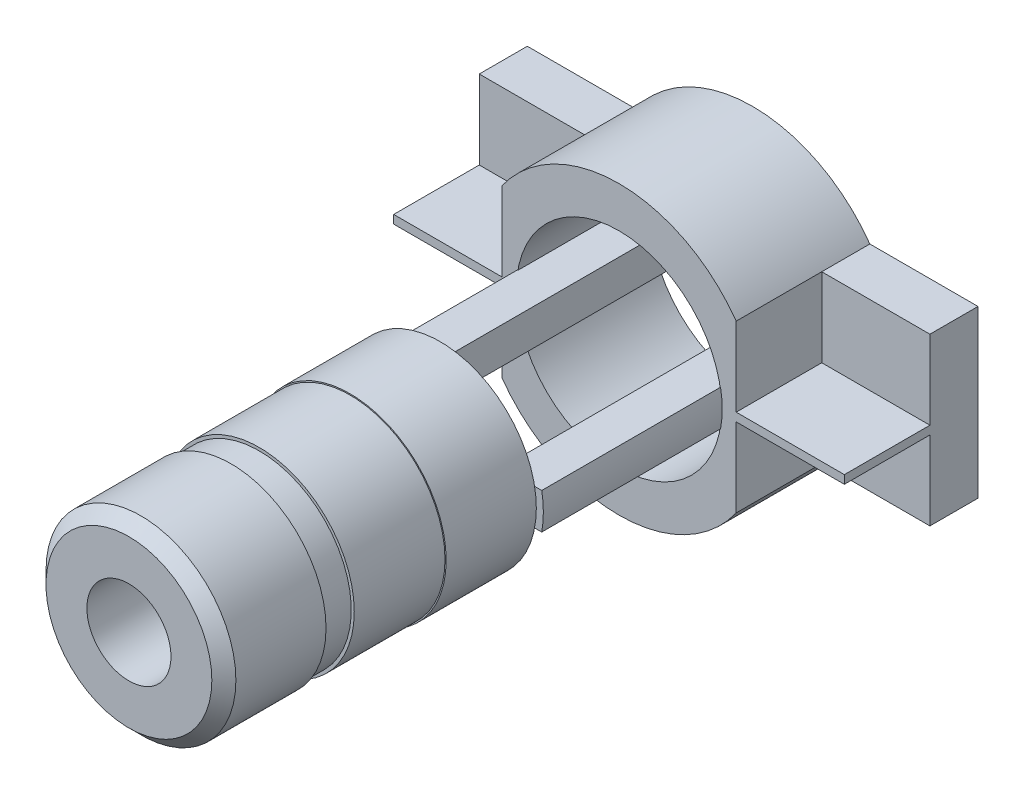
SolidWorks part; units mm, degrees
material "ASTM A36 Steel"
ref_plane "Front Plane" through (0, 0, 0) normal (0, 0, 1) x (1, 0, 0)
ref_plane "Top Plane" through (0, 0, 0) normal (0, 1, 0) x (1, 0, 0)
ref_plane "Right Plane" through (0, 0, 0) normal (1, 0, 0) x (0, 0, -1)
sketch "Sketch1" plane through (0, 0, 0) normal (0, 0, 1) x (1, 0, 0)
  circle A0 centre (0, 0) radius 7.9
  circle A1 centre (0, 0) radius 3.5
  dimension "D1" = 15.8
  dimension "D2" = 7
extrude "Boss-Extrude1" add sketch "Sketch1" along normal blind 18.4
chamfer "Chamfer1" distance 1 angle 45 1 edges at (7.9, 0, 18.4)
ref_plane "Plane7" [suppressed] through (0, 0, 7.5) normal (0, 0, -1) x (-1, 0, 0)
ref_plane "Plane8" through (0, 0, 9.9) normal (0, 0, -1) x (-1, 0, 0)
sketch "Sketch19" plane through (0, 0, 9.9) normal (0, 0, -1) x (-1, 0, 0)
  circle A0 centre (0, 0) radius 7.65
  circle A1 centre (0, 0) radius 7.9
  dimension "D1" = 15.3
extrude "Cut-Extrude6" cut sketch "Sketch19" along normal blind 2.35
sketch "Sketch20" plane through (0, 0, 0) normal (0, 0, -1) x (-1, 0, 0)
  circle A0 centre (0, 0) radius 7.9
  circle A1 centre (0, 0) radius 4.5
  dimension "D1" = 9
extrude "Boss-Extrude3" [suppressed] add sketch "Sketch20" along normal blind 28.6 separate body
sketch "Sketch21" [suppressed] plane through (0, 0, -28.6) normal (0, 0, -1) x (-1, 0, 0)
  line L1 (0, 3.0042) -> (-7.3065, 3.0042)
  line L9 (-7.3081, -3.0004) -> (0, -3.0004)
  line L12 (0, -3.0004) -> (7.3081, -3.0004)
  line L13 (0, 3.0042) -> (7.3065, 3.0042)
  circle A0 centre (0, 0) radius 7.9 construction
  arc A1 (-7.3065, 3.0042) -> (7.3065, 3.0042) centre (0, 0) cw
  arc A2 (-7.3081, -3.0004) -> (7.3081, -3.0004) centre (0, 0) ccw
extrude "Cut-Extrude7" [suppressed] cut sketch "Sketch21" against normal blind 28.6
ref_plane "Plane9" [suppressed] through (0, 0, -28.6) normal (0, 0, -1) x (-1, 0, 0)
sketch "Sketch22" [suppressed] plane through (0, 0, -28.6) normal (0, 0, -1) x (-1, 0, 0)
  circle A0 centre (0, 0) radius 12
  dimension "D1" = 24
extrude "Boss-Extrude4" [suppressed] add sketch "Sketch22" along normal blind 6
sketch "Sketch23" [suppressed] plane through (0, 0, -34.6) normal (0, 0, -1) x (-1, 0, 0)
  circle A0 centre (0, 0) radius 4.5
  dimension "D1" = 9
extrude "Cut-Extrude8" [suppressed] cut sketch "Sketch23" against normal up to next
sketch "Sketch24" plane through (0, 0, 0) normal (0, 0, -1) x (-1, 0, 0)
  circle A0 centre (0, 0) radius 8
  dimension "D1" = 16
extrude "Boss-Extrude5" add sketch "Sketch24" along normal blind 7.5 separate body
sketch "Sketch25" plane through (0, 0, -7.5) normal (0, 0, -1) x (-1, 0, 0)
  line L3 (-5.15, 1.5) -> (-8.45, 1.5)
  line L4 (-5.15, -1.5) -> (-8.45, -1.5)
  line L5 (-0.0834, 0) -> (-5.15, 0) construction
  line L6 (-5.15, 1.5) -> (-5.15, 0)
  line L7 (-5.15, 0) -> (-5.15, -1.5)
  line L8 (0, 8.69) -> (0, -8.69) construction
  line L9 (5.15, 1.5) -> (5.15, 0)
  line L10 (5.15, 1.5) -> (8.45, 1.5)
  line L11 (5.15, -1.5) -> (8.45, -1.5)
  line L12 (5.15, 0) -> (5.15, -1.5)
  arc A0 (8.5834, 0) -> (8.45, 1.5) centre (0.0834, 0) ccw
  arc A1 (-8.5834, 0) -> (-8.45, 1.5) centre (-0.0834, 0) cw
  arc A2 (-8.5834, 0) -> (-8.45, -1.5) centre (-0.0834, 0) ccw
  arc A3 (8.5834, 0) -> (8.45, -1.5) centre (0.0834, 0) cw
  dimension "D5" = 8.5
  dimension "D1" = 3.3
  dimension "D2" = 3.3
  dimension "D3" = 3
  dimension "D4" = 5.15
extrude "Boss-Extrude6" add sketch "Sketch25" along normal blind 26 separate body
ref_plane "Plane10" through (0, 0, -33.5) normal (0, 0, -1) x (-1, 0, 0)
sketch "Sketch26" plane through (0, 0, -33.5) normal (0, 0, -1) x (-1, 0, 0)
  circle A0 centre (0, 0) radius 11.95
  circle A1 centre (0, 0) radius 8.55
  dimension "D1" = 23.9
  dimension "D2" = 17.1
extrude "Boss-Extrude7" add sketch "Sketch26" against normal blind 11.12 separate body
sketch "Sketch27" plane through (0, 0, -22.38) normal (0, 0, 1) x (1, 0, 0)
  line L2 (-9.75, 0) -> (-9.75, 6.9094)
  line L3 (-9.75, 0) -> (-9.75, -6.9094)
  line L4 (9.75, 0) -> (9.75, 6.9094)
  line L5 (9.75, 0) -> (9.75, -6.9094)
  circle A0 centre (0, 0) radius 11.95 construction
  arc A1 (-9.75, 6.9094) -> (-9.75, -6.9094) centre (0, 0) ccw
  arc A2 (9.75, 6.9094) -> (9.75, -6.9094) centre (0, 0) cw
extrude "Cut-Extrude9" cut sketch "Sketch27" against normal through all
sketch "Sketch28" plane through (0, 0, -7.5) normal (0, 0, -1) x (-1, 0, 0)
  circle A0 centre (0, 0) radius 3.5
  dimension "D1" = 7
extrude "Cut-Extrude10" cut sketch "Sketch28" against normal through all
sketch "Sketch29" plane through (-9.75, 0, 0) normal (-1, 0, 0) x (0, 0, 1)
  line L0 (-33.5, 6.9094) -> (-29.5, 6.9094)
  line L1 (-33.5, 6.9094) -> (-22.38, 6.9094) construction
  line L2 (-29.5, 6.9094) -> (-29.5, -6.9094)
  line L3 (-33.5, -6.9094) -> (-22.38, -6.9094) construction
  line L4 (-29.5, -6.9094) -> (-33.5, -6.9094)
  line L5 (-33.5, -6.9094) -> (-33.5, 6.9094)
  dimension "D1" = 4
extrude "Boss-Extrude8" add sketch "Sketch29" along normal blind 9
sketch "Sketch30" plane through (9.75, 0, 0) normal (1, 0, 0) x (0, 0, -1)
  line L0 (33.5, 6.9094) -> (29.5, 6.9094)
  line L1 (33.5, 6.9094) -> (22.38, 6.9094) construction
  line L2 (29.5, 6.9094) -> (29.5, -6.9094)
  line L3 (33.5, -6.9094) -> (22.38, -6.9094) construction
  line L4 (29.5, -6.9094) -> (33.5, -6.9094)
  line L5 (33.5, -6.9094) -> (33.5, 6.9094)
  dimension "D1" = 4
extrude "Boss-Extrude9" add sketch "Sketch30" along normal blind 9
sketch "Sketch31" plane through (9.75, 0, 0) normal (1, 0, 0) x (0, 0, -1)
  line L0 (22.38, 0) -> (22.38, 0.35)
  line L1 (22.38, 6.9094) -> (22.38, -6.9094) construction
  line L2 (22.38, 0.35) -> (29.5, 0.35)
  line L3 (29.5, 6.9094) -> (29.5, -6.9094) construction
  line L4 (22.38, 0) -> (22.38, -0.35)
  line L5 (22.38, -0.35) -> (29.5, -0.35)
  line L6 (29.5, 6.9094) -> (29.5, -6.9094) construction
  line L7 (29.5, 0.35) -> (29.5, -0.35)
  dimension "D1" = 0.35
  dimension "D2" = 0.35
extrude "Boss-Extrude10" add sketch "Sketch31" along normal blind 9
sketch "Sketch32" plane through (-9.75, 0, 0) normal (-1, 0, 0) x (0, 0, 1)
  line L0 (-22.38, 0) -> (-22.38, 0.35)
  line L1 (-22.38, -6.9094) -> (-22.38, 6.9094) construction
  line L2 (-22.38, 0) -> (-22.38, -0.35)
  line L3 (-22.38, 0.35) -> (-29.5, 0.35)
  line L4 (-29.5, -6.9094) -> (-29.5, 6.9094) construction
  line L5 (-22.38, -0.35) -> (-29.5, -0.35)
  line L6 (-29.5, -6.9094) -> (-29.5, 6.9094) construction
  line L7 (-29.5, 0.35) -> (-29.5, -0.35)
  dimension "D1" = 0.35
  dimension "D2" = 0.35
extrude "Boss-Extrude11" add sketch "Sketch32" along normal blind 9
equation "\"D2@Sketch25\"=\"D1@Sketch25\""
